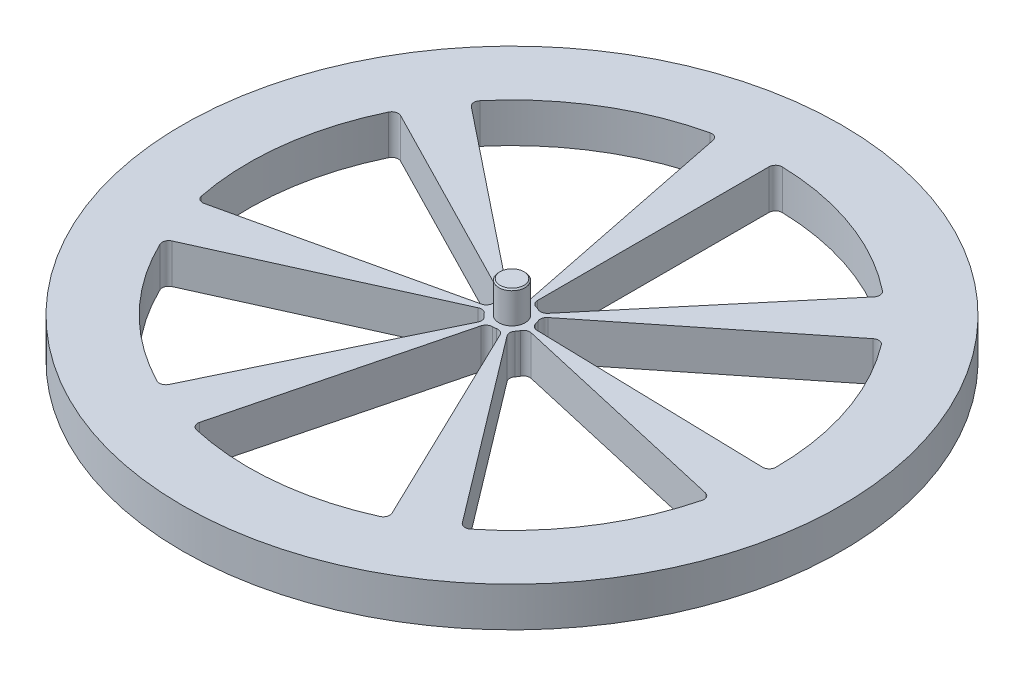
SolidWorks part; units mm, degrees
ref_plane "Front Plane" through (0, 0, 0) normal (0, 0, 1) x (1, 0, 0)
ref_plane "Top Plane" through (0, 0, 0) normal (0, 1, 0) x (1, 0, 0)
ref_plane "Right Plane" through (0, 0, 0) normal (1, 0, 0) x (0, 0, -1)
sketch "Sketch1" plane through (0, 0, 0) normal (0, 1, 0) x (1, 0, 0)
  circle A0 centre (0, 0) radius 250
  dimension "D1" = 500
extrude "Boss-Extrude1" add sketch "Sketch1" along normal blind 30
sketch "Sketch2" plane through (0, 30, 0) normal (0, 1, 0) x (1, 0, 0)
  line L0 (0, 15) -> (0, 200)
  line L1 (9.6418, 11.4907) -> (128.5575, 153.2089)
  arc A0 (9.6418, 11.4907) -> (0, 15) centre (0, 0) ccw
  arc A1 (128.5575, 153.2089) -> (0, 200) centre (0, 0) ccw
  circle A2 centre (0, 0) radius 250 construction
  dimension "D1" = 15
  dimension "D2" = 50
  dimension "D3" = 40
extrude "Cut-Extrude1" cut sketch "Sketch2" against normal through all
fillet "Fillet1" radius 5 4 edges at (128.5575, 15, -153.2089) (0, 15, -200) (9.6418, 15, -11.4907) (0, 15, -15)
pattern_circular "CirPattern1" count 7 over 360 about axis through (0, 30, 0) along (0, -1, 0) of "Cut-Extrude1", "Fillet1"
sketch "Sketch3" plane through (0, 30, 0) normal (0, 1, 0) x (1, 0, 0)
  circle A0 centre (0, 0) radius 10
  dimension "D1" = 20
extrude "Boss-Extrude2" add sketch "Sketch3" along normal blind 24.1
chamfer "Chamfer1" distance 1 angle 45 1 edges at (0, 54.1, 10)
